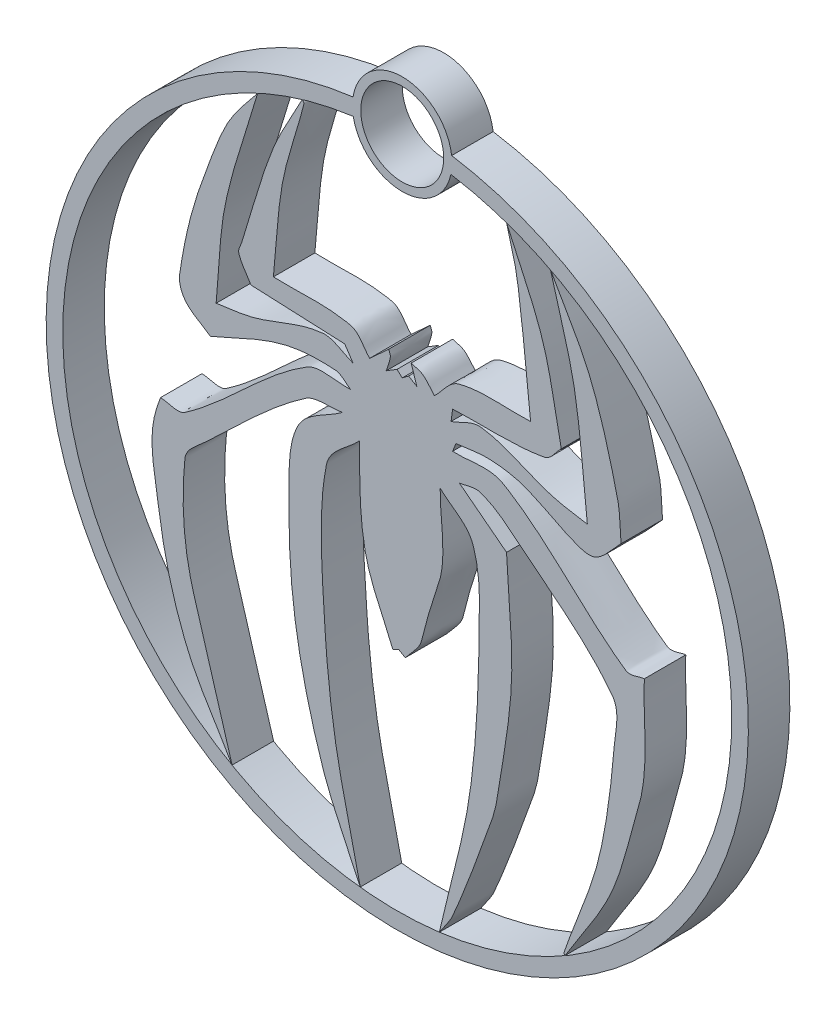
SolidWorks part; units mm, degrees
ref_plane "Front Plane" through (0, 0, 0) normal (0, 0, 1) x (1, 0, 0)
ref_plane "Top Plane" through (0, 0, 0) normal (0, 1, 0) x (1, 0, 0)
ref_plane "Right Plane" through (0, 0, 0) normal (1, 0, 0) x (0, 0, -1)
sketch "Sketch1" plane through (0, 0, 0) normal (0, 0, 1) x (1, 0, 0)
  line L0 (290.5, 765.5) -> (1452.5, 765.5) construction
  line L1 (830, 897) -> (853, 918)
  line L2 (850, 894) -> (863, 902)
  line L3 (863, 902) -> (869.2904, 896.2178)
  line L4 (869.2904, 896.2178) -> (877, 902)
  line L5 (877, 902) -> (887, 896)
  line L6 (887, 896) -> (880, 917)
  line L7 (930, 894) -> (928.107, 880.1521)
  line L8 (934, 860) -> (930, 850)
  line L9 (938, 821) -> (995, 777)
  line L10 (873, 606) -> (864.8228, 610.6727)
  line L11 (864.8228, 610.6727) -> (858, 607)
  line L12 (810, 882) -> (800, 897)
  line L13 (800, 897) -> (687, 902)
  line L14 (830, 897) -> (853, 918)
  line L15 (850, 894) -> (863, 902)
  line L16 (863, 902) -> (869.2904, 896.2178)
  line L17 (869.2904, 896.2178) -> (877, 902)
  line L18 (877, 902) -> (887, 896)
  line L19 (887, 896) -> (880, 917)
  line L20 (930, 894) -> (928.107, 880.1521)
  line L21 (934, 860) -> (930, 850)
  line L22 (938, 821) -> (995, 777)
  line L23 (873, 606) -> (864.8228, 610.6727)
  line L24 (864.8228, 610.6727) -> (858, 607)
  line L25 (810, 882) -> (800, 897)
  line L26 (800, 897) -> (687, 902)
  arc A0 (810.2984, 1139.6499) -> (927.9381, 1137.9352) centre (863.305, 739.9749) ccw
  arc A1 (809.9963, 1159.7784) -> (928.8268, 1158.0463) centre (863.305, 739.9749) ccw
  circle A2 centre (869.2904, 1150.6019) radius 50
  circle A3 centre (869.2904, 1150.6019) radius 60
  circle A5 centre (863.305, 739.9749) radius 403.1747 construction
  circle A6 centre (863.305, 739.9749) radius 423.1747 construction
  spline S0 degree 3 poles (748.8079, 1126.5499) (749.5, 1125.458) (751.1878, 1124.5307) (750.8841, 1123.2741) (743.1608, 1091.3225) (730.9965, 1060.4353) (725.0138, 1028.1125) (718.6624, 993.7975) (717.6713, 958.7042) (714, 924) knots 0 0 0 0 1 1 1 2 2 2 3 3 3 3
  spline S1 degree 3 poles (714, 924) (745, 922.6667) (776.7792, 927.0342) (807, 920) (817.56, 917.5421) (822.3333, 904.6667) (830, 897) knots 0 0 0 0 1 1 1 2 2 2 2
  spline S2 degree 3 poles (853, 918) (853.6667, 915.6667) (855.301, 913.408) (855, 911) (854.2674, 905.1389) (851.6667, 899.6667) (850, 894) knots 0 0 0 0 1 1 1 2 2 2 2
  spline S3 degree 3 poles (880, 917) (884.6667, 915.3333) (889.9677, 914.8802) (894, 912) (899.5655, 908.0247) (903.3333, 902) (908, 897) knots 0 0 0 0 1 1 1 2 2 2 2
  spline S4 degree 3 poles (908, 897) (918, 906) (925.0025, 920.5265) (938, 924) (965.7247, 931.4092) (995.3333, 926.6667) (1024, 928) knots 0 0 0 0 1 1 1 2 2 2 2
  spline S5 degree 3 poles (1024, 928) (1018.6673, 974.6437) (1014.9767, 1021.5046) (1008.0019, 1067.9311) (1005.2945, 1085.9528) (999.334, 1103.3332) (995, 1121.0343) knots 0 0 0 0 1 1 1 2 2 2 2
  spline S6 degree 3 poles (995, 1121.0343) (1009.3388, 1087.8237) (1026.8334, 1055.8043) (1038.0164, 1021.4024) (1048.9318, 987.8234) (1053.3388, 952.4675) (1061, 918) knots 0 0 0 0 1 1 1 2 2 2 2
  spline S7 degree 3 poles (1061, 918) (1054, 911.6667) (1049.2853, 900.7011) (1040, 899) (1003.8964, 892.3856) (966.6667, 895.6667) (930, 894) knots 0 0 0 0 1 1 1 2 2 2 2
  spline S8 degree 3 poles (1092.4006, 855) (1078.1472, 857.7806) (1063.5825, 859.2782) (1049.6406, 863.3418) (1021.195, 871.6327) (994.8454, 887.9286) (965.4956, 891.9882) (952.5464, 893.7793) (940.5699, 884.0975) (928.107, 880.1521) knots 0 0 0 0 1 1 1 2 2 2 3 3 3 3
  spline S9 degree 3 poles (1092.4006, 855) (1087.1155, 900.0345) (1084.6871, 945.4969) (1076.5453, 990.1035) (1069.8437, 1026.8198) (1057.502, 1062.2792) (1047.9803, 1098.367) knots 0 0 0 0 1 1 1 2 2 2 2
  spline S10 degree 3 poles (1047.9803, 1098.367) (1063.8337, 1069.0339) (1082.9299, 1041.234) (1095.5406, 1010.3676) (1109.9081, 975.2013) (1119.5998, 938.2044) (1128.5037, 901.2745) (1132.1361, 886.2088) (1131.5012, 870.4248) (1133, 855) knots 0 0 0 0 1 1 1 2 2 2 3 3 3 3
  spline S11 degree 3 poles (1133, 855) (1123, 845.3333) (1115.246, 832.594) (1103, 826) (1096.5365, 822.5197) (1087.9239, 824.5609) (1081, 827) (1058.2068, 835.0294) (1037.8617, 849.1678) (1015, 857) (1001.573, 861.6) (987.1834, 863.4747) (973, 864) (959.9408, 864.4837) (947, 861.3333) (934, 860) knots 0 0 0 0 1 1 1 2 2 2 3 3 3 4 4 4 5 5 5 5
  spline S12 degree 3 poles (930, 850) (950.6667, 848.6667) (974.2115, 856.6047) (992, 846) (1046.1099, 813.7422) (1086.349, 762.064) (1138, 726) (1144.3097, 721.5944) (1153.3333, 727.3333) (1161, 728) knots 0 0 0 0 1 1 1 2 2 2 3 3 3 3
  spline S13 degree 3 poles (1161, 728) (1159.3079, 682.3854) (1167.3998, 634.9133) (1154.1466, 591.2337) (1143.4212, 555.8856) (1136.4966, 519.0935) (1121.5144, 485.3288) (1106.6784, 451.8936) (1084.0567, 422.4876) (1065.3278, 391.0671) knots 0 0 0 0 1 1 1 2 2 2 3 3 3 3
  spline S14 degree 3 poles (1065.3278, 391.0671) (1065.0055, 392.1211) (1064.0105, 393.1841) (1064.3609, 394.2291) (1077.6394, 433.8371) (1096.045, 471.8607) (1106.0139, 512.4283) (1116.3202, 554.3693) (1121.0733, 597.5914) (1124.9051, 640.6098) (1126.4255, 657.6777) (1132.3929, 678.3079) (1122.0033, 691.9344) (1090.2335, 733.6022) (1045.643, 763.7987) (1005.3968, 797.3513) (992.9086, 807.7625) (979.5528, 818.0999) (964.2111, 823.4832) (955.9299, 826.3889) (946.737, 821.8277) (938, 821) knots 0 0 0 0 1 1 1 2 2 2 3 3 3 4 4 4 5 5 5 6 6 6 7 7 7 7
  spline S15 degree 3 poles (995, 777) (997, 733) (1002.8547, 689.0064) (1001, 645) (999.1737, 601.6667) (990.5539, 558.8737) (984, 516) (982.5462, 506.4899) (980.2242, 497.0642) (977, 488) (962.5391, 447.3457) (947.9003, 406.7023) (931, 367) (926.8345, 357.2143) (919.6667, 349) (914, 340) knots 0 0 0 0 1 1 1 2 2 2 3 3 3 4 4 4 5 5 5 5
  spline S16 degree 3 poles (914, 340) (926.3333, 395) (943.0749, 449.1941) (951, 505) (959.1244, 562.2091) (961.3359, 620.2207) (962, 678) (962.3385, 707.4524) (964.2941, 738.4031) (954, 766) (947.6565, 783.006) (928, 791.3333) (915, 804) knots 0 0 0 0 1 1 1 2 2 2 3 3 3 4 4 4 4
  spline S17 degree 3 poles (915, 804) (914.6529, 770.3285) (923.8655, 734.8721) (913, 703) (882.7955, 614.4) (903.0097, 641.4661) (873, 606) knots 0 0 0 0 1 1 1 2 2 2 2
  spline S18 degree 3 poles (858, 607) (847.3333, 633.6667) (832.6151, 659.0513) (826, 687) (816.9198, 725.3637) (818, 765.5764) (818, 805) knots 0 0 0 0 1 1 1 2 2 2 2
  spline S19 degree 3 poles (818, 805) (804.6123, 789.89) (781.6929, 779.486) (777.8368, 759.6701) (767.0122, 704.0439) (772.7099, 646.2385) (776.0979, 589.6703) (779.3554, 535.2829) (786.2775, 480.8555) (798.4877, 427.7564) (805.2687, 398.2673) (811.9944, 368.7654) (818.7477, 339.2698) knots 0 0 0 0 1 1 1 2 2 2 3 3 3 4 4 4 4
  spline S20 degree 3 poles (818.7477, 339.2698) (803.6176, 373.4448) (785.1308, 406.3231) (773.3575, 441.7948) (759.1165, 484.701) (747.9358, 528.8294) (741.0038, 573.5026) (734.3599, 616.3193) (732.2243, 659.9047) (732.7901, 703.2302) (733.1436, 730.2994) (731.0402, 759.799) (743.7489, 783.7022) (754.1988, 803.3569) (779.2496, 810.5674) (797, 824) knots 0 0 0 0 1 1 1 2 2 2 3 3 3 4 4 4 5 5 5 5
  spline S21 degree 3 poles (797, 824) (782.1863, 821.5091) (764.9363, 825.0389) (752.5588, 816.5273) (708.444, 786.1909) (670.9697, 747.1163) (631.9257, 710.4835) (622.4035, 701.5493) (608.4001, 693.1213) (607.1751, 680.1216) (602.9503, 635.2857) (605.1611, 588.6313) (617.939, 545.4476) (633.3407, 493.3966) (648.7242, 441.3401) (664.2954, 389.3397) knots 0 0 0 0 1 1 1 2 2 2 3 3 3 4 4 4 5 5 5 5
  spline S22 degree 3 poles (664.2954, 389.3397) (645.926, 421.8829) (623.4165, 452.4148) (609.1873, 486.9694) (594.5104, 522.6112) (584.1309, 560.2917) (578.2148, 598.3803) (567.7535, 665.7311) (560.9693, 686.5641) (578, 730) knots 0 0 0 0 1 1 1 2 2 2 3 3 3 3
  spline S23 degree 3 poles (578, 730) (587.6667, 729.6667) (599.0084, 723.5512) (607, 729) (659.4363, 764.752) (700.0611, 816.5579) (754, 850) (769.039, 859.3242) (789.3333, 852) (807, 853) knots 0 0 0 0 1 1 1 2 2 2 3 3 3 3
  spline S24 degree 3 poles (807, 853) (801, 856.6667) (796.0134, 863.493) (789, 864) (767.3259, 865.5668) (745.0061, 864.5645) (724, 859) (694.0821, 851.0747) (666.6667, 835.6667) (638, 824) knots 0 0 0 0 1 1 1 2 2 2 3 3 3 3
  spline S25 degree 3 poles (638, 824) (628, 831.3333) (615.7723, 836.3372) (608, 846) (602.777, 852.4934) (599.8127, 861.7517) (601, 870) (606.2755, 906.6508) (614.5152, 943.1397) (627, 978) (657.4083, 1062.9064) (658.7168, 1061.1796) (695, 1106) knots 0 0 0 0 1 1 1 2 2 2 3 3 3 4 4 4 4
  spline S26 degree 3 poles (695, 1106) (682, 1061) (665.403, 1016.8866) (656, 971) (648.6692, 935.2255) (648.6667, 898.3333) (645, 862) knots 0 0 0 0 1 1 1 2 2 2 2
  spline S27 degree 3 poles (645, 862) (659.3333, 864.3333) (673.9378, 865.3746) (688, 869) (716.691, 876.3969) (743.5376, 891.8606) (773, 895) (785.9989, 896.3851) (797.6667, 886.3333) (810, 882) knots 0 0 0 0 1 1 1 2 2 2 3 3 3 3
  spline S28 degree 3 poles (687, 902) (682.1323, 910.6119) (675.1585, 918.3366) (672.3968, 927.8357) (671.1674, 932.0645) (674.4525, 936.4076) (675.7753, 940.6082) (687.8517, 978.9585) (697.8907, 1018.0496) (712.5896, 1055.4732) (722.3108, 1080.2234) (736.7351, 1102.8577) (748.8079, 1126.5499) knots 0 0 0 0 1 1 1 2 2 2 3 3 3 4 4 4 4
  spline S29 degree 3 poles (748.8079, 1126.5499) (749.5, 1125.458) (751.1878, 1124.5307) (750.8841, 1123.2741) (743.1608, 1091.3225) (730.9965, 1060.4353) (725.0138, 1028.1125) (718.6624, 993.7975) (717.6713, 958.7042) (714, 924) knots 0 0 0 0 1 1 1 2 2 2 3 3 3 3
  spline S30 degree 3 poles (714, 924) (745, 922.6667) (776.7792, 927.0342) (807, 920) (817.56, 917.5421) (822.3333, 904.6667) (830, 897) knots 0 0 0 0 1 1 1 2 2 2 2
  spline S31 degree 3 poles (853, 918) (853.6667, 915.6667) (855.301, 913.408) (855, 911) (854.2674, 905.1389) (851.6667, 899.6667) (850, 894) knots 0 0 0 0 1 1 1 2 2 2 2
  spline S32 degree 3 poles (880, 917) (884.6667, 915.3333) (889.9677, 914.8802) (894, 912) (899.5655, 908.0247) (903.3333, 902) (908, 897) knots 0 0 0 0 1 1 1 2 2 2 2
  spline S33 degree 3 poles (908, 897) (918, 906) (925.0025, 920.5265) (938, 924) (965.7247, 931.4092) (995.3333, 926.6667) (1024, 928) knots 0 0 0 0 1 1 1 2 2 2 2
  spline S34 degree 3 poles (1024, 928) (1018.6673, 974.6437) (1014.9767, 1021.5046) (1008.0019, 1067.9311) (1005.2945, 1085.9528) (999.334, 1103.3332) (995, 1121.0343) knots 0 0 0 0 1 1 1 2 2 2 2
  spline S35 degree 3 poles (995, 1121.0343) (1009.3388, 1087.8237) (1026.8334, 1055.8043) (1038.0164, 1021.4024) (1048.9318, 987.8234) (1053.3388, 952.4675) (1061, 918) knots 0 0 0 0 1 1 1 2 2 2 2
  spline S36 degree 3 poles (1061, 918) (1054, 911.6667) (1049.2853, 900.7011) (1040, 899) (1003.8964, 892.3856) (966.6667, 895.6667) (930, 894) knots 0 0 0 0 1 1 1 2 2 2 2
  spline S38 degree 3 poles (1092.4006, 855) (1087.1155, 900.0345) (1084.6871, 945.4969) (1076.5453, 990.1035) (1069.8437, 1026.8198) (1057.502, 1062.2792) (1047.9803, 1098.367) knots 0 0 0 0 1 1 1 2 2 2 2
  spline S39 degree 3 poles (1047.9803, 1098.367) (1063.8337, 1069.0339) (1082.9299, 1041.234) (1095.5406, 1010.3676) (1109.9081, 975.2013) (1119.5998, 938.2044) (1128.5037, 901.2745) (1132.1361, 886.2088) (1131.5012, 870.4248) (1133, 855) knots 0 0 0 0 1 1 1 2 2 2 3 3 3 3
  spline S40 degree 3 poles (1133, 855) (1123, 845.3333) (1115.246, 832.594) (1103, 826) (1096.5365, 822.5197) (1087.9239, 824.5609) (1081, 827) (1058.2068, 835.0294) (1037.8617, 849.1678) (1015, 857) (1001.573, 861.6) (987.1834, 863.4747) (973, 864) (959.9408, 864.4837) (947, 861.3333) (934, 860) knots 0 0 0 0 1 1 1 2 2 2 3 3 3 4 4 4 5 5 5 5
  spline S41 degree 3 poles (930, 850) (950.6667, 848.6667) (974.2115, 856.6047) (992, 846) (1046.1099, 813.7422) (1086.349, 762.064) (1138, 726) (1144.3097, 721.5944) (1153.3333, 727.3333) (1161, 728) knots 0 0 0 0 1 1 1 2 2 2 3 3 3 3
  spline S42 degree 3 poles (1161, 728) (1159.3079, 682.3854) (1167.3998, 634.9133) (1154.1466, 591.2337) (1143.4212, 555.8856) (1136.4966, 519.0935) (1121.5144, 485.3288) (1106.6784, 451.8936) (1084.0567, 422.4876) (1065.3278, 391.0671) knots 0 0 0 0 1 1 1 2 2 2 3 3 3 3
  spline S43 degree 3 poles (1065.3278, 391.0671) (1065.0055, 392.1211) (1064.0105, 393.1841) (1064.3609, 394.2291) (1077.6394, 433.8371) (1096.045, 471.8607) (1106.0139, 512.4283) (1116.3202, 554.3693) (1121.0733, 597.5914) (1124.9051, 640.6098) (1126.4255, 657.6777) (1132.3929, 678.3079) (1122.0033, 691.9344) (1090.2335, 733.6022) (1045.643, 763.7987) (1005.3968, 797.3513) (992.9086, 807.7625) (979.5528, 818.0999) (964.2111, 823.4832) (955.9299, 826.3889) (946.737, 821.8277) (938, 821) knots 0 0 0 0 1 1 1 2 2 2 3 3 3 4 4 4 5 5 5 6 6 6 7 7 7 7
  spline S44 degree 3 poles (995, 777) (997, 733) (1002.8547, 689.0064) (1001, 645) (999.1737, 601.6667) (990.5539, 558.8737) (984, 516) (982.5462, 506.4899) (980.2242, 497.0642) (977, 488) (962.5391, 447.3457) (947.9003, 406.7023) (931, 367) (926.8345, 357.2143) (919.6667, 349) (914, 340) knots 0 0 0 0 1 1 1 2 2 2 3 3 3 4 4 4 5 5 5 5
  spline S45 degree 3 poles (914, 340) (926.3333, 395) (943.0749, 449.1941) (951, 505) (959.1244, 562.2091) (961.3359, 620.2207) (962, 678) (962.3385, 707.4524) (964.2941, 738.4031) (954, 766) (947.6565, 783.006) (928, 791.3333) (915, 804) knots 0 0 0 0 1 1 1 2 2 2 3 3 3 4 4 4 4
  spline S46 degree 3 poles (915, 804) (914.6529, 770.3285) (923.8655, 734.8721) (913, 703) (882.7955, 614.4) (903.0097, 641.4661) (873, 606) knots 0 0 0 0 1 1 1 2 2 2 2
  spline S47 degree 3 poles (858, 607) (847.3333, 633.6667) (832.6151, 659.0513) (826, 687) (816.9198, 725.3637) (818, 765.5764) (818, 805) knots 0 0 0 0 1 1 1 2 2 2 2
  spline S48 degree 3 poles (818, 805) (804.6123, 789.89) (781.6929, 779.486) (777.8368, 759.6701) (767.0122, 704.0439) (772.7099, 646.2385) (776.0979, 589.6703) (779.3554, 535.2829) (786.2775, 480.8555) (798.4877, 427.7564) (805.2687, 398.2673) (811.9944, 368.7654) (818.7477, 339.2698) knots 0 0 0 0 1 1 1 2 2 2 3 3 3 4 4 4 4
  spline S49 degree 3 poles (818.7477, 339.2698) (803.6176, 373.4448) (785.1308, 406.3231) (773.3575, 441.7948) (759.1165, 484.701) (747.9358, 528.8294) (741.0038, 573.5026) (734.3599, 616.3193) (732.2243, 659.9047) (732.7901, 703.2302) (733.1436, 730.2994) (731.0402, 759.799) (743.7489, 783.7022) (754.1988, 803.3569) (779.2496, 810.5674) (797, 824) knots 0 0 0 0 1 1 1 2 2 2 3 3 3 4 4 4 5 5 5 5
  spline S50 degree 3 poles (797, 824) (782.1863, 821.5091) (764.9363, 825.0389) (752.5588, 816.5273) (708.444, 786.1909) (670.9697, 747.1163) (631.9257, 710.4835) (622.4035, 701.5493) (608.4001, 693.1213) (607.1751, 680.1216) (602.9503, 635.2857) (605.1611, 588.6313) (617.939, 545.4476) (633.3407, 493.3966) (648.7242, 441.3401) (664.2954, 389.3397) knots 0 0 0 0 1 1 1 2 2 2 3 3 3 4 4 4 5 5 5 5
  spline S51 degree 3 poles (664.2954, 389.3397) (645.926, 421.8829) (623.4165, 452.4148) (609.1873, 486.9694) (594.5104, 522.6112) (584.1309, 560.2917) (578.2148, 598.3803) (567.7535, 665.7311) (560.9693, 686.5641) (578, 730) knots 0 0 0 0 1 1 1 2 2 2 3 3 3 3
  spline S52 degree 3 poles (578, 730) (587.6667, 729.6667) (599.0084, 723.5512) (607, 729) (659.4363, 764.752) (700.0611, 816.5579) (754, 850) (769.039, 859.3242) (789.3333, 852) (807, 853) knots 0 0 0 0 1 1 1 2 2 2 3 3 3 3
  spline S53 degree 3 poles (807, 853) (801, 856.6667) (796.0134, 863.493) (789, 864) (767.3259, 865.5668) (745.0061, 864.5645) (724, 859) (694.0821, 851.0747) (666.6667, 835.6667) (638, 824) knots 0 0 0 0 1 1 1 2 2 2 3 3 3 3
  spline S54 degree 3 poles (638, 824) (628, 831.3333) (615.7723, 836.3372) (608, 846) (602.777, 852.4934) (599.8127, 861.7517) (601, 870) (606.2755, 906.6508) (614.5152, 943.1397) (627, 978) (657.4083, 1062.9064) (658.7168, 1061.1796) (695, 1106) knots 0 0 0 0 1 1 1 2 2 2 3 3 3 4 4 4 4
  spline S55 degree 3 poles (695, 1106) (682, 1061) (665.403, 1016.8866) (656, 971) (648.6692, 935.2255) (648.6667, 898.3333) (645, 862) knots 0 0 0 0 1 1 1 2 2 2 2
  spline S56 degree 3 poles (645, 862) (659.3333, 864.3333) (673.9378, 865.3746) (688, 869) (716.691, 876.3969) (743.5376, 891.8606) (773, 895) (785.9989, 896.3851) (797.6667, 886.3333) (810, 882) knots 0 0 0 0 1 1 1 2 2 2 3 3 3 3
  spline S57 degree 3 poles (687, 902) (682.1323, 910.6119) (675.1585, 918.3366) (672.3968, 927.8357) (671.1674, 932.0645) (674.4525, 936.4076) (675.7753, 940.6082) (687.8517, 978.9585) (697.8907, 1018.0496) (712.5896, 1055.4732) (722.3108, 1080.2234) (736.7351, 1102.8577) (748.8079, 1126.5499) knots 0 0 0 0 1 1 1 2 2 2 3 3 3 4 4 4 4
  point P46 (1248.8629, 857.8517)
  point P48 (1286.4798, 739.9749)
  dimension "D1" = 20
  dimension "D3" = 10
extrude "Boss-Extrude1" add sketch "Sketch1" along normal blind 50 contours S52 L0 S21 S49 S19 S47 S17 S45 S15 L9 S43 S12 L8 S11 S10 S9 S8 L7 S7 S6 S5 S4 S3 L6 L5 L4 L3 L2 S2 L1 S1 S0 S28 L13 L12 S27 S26 S25 S24 | L0 S20 S48 | L0 S23 S22 S50 | L0 S18 L11 L10 S46 | L0 S16 S44 | L0 S14 S13 S41 region at (875.5138, 778.2103, 0)
extrude "Boss-Extrude2" add sketch "Sketch1<4>" along normal blind 50 separate body contours A1 L0 A0 | L0 A1 A0 | A3 | A2 region at (450.8861, 787.2539, 0)
sketch "Sketch1<4>" plane through (0, 0, 0) normal (0, 0, 1) x (1, 0, 0) same geometry as "Sketch1"
